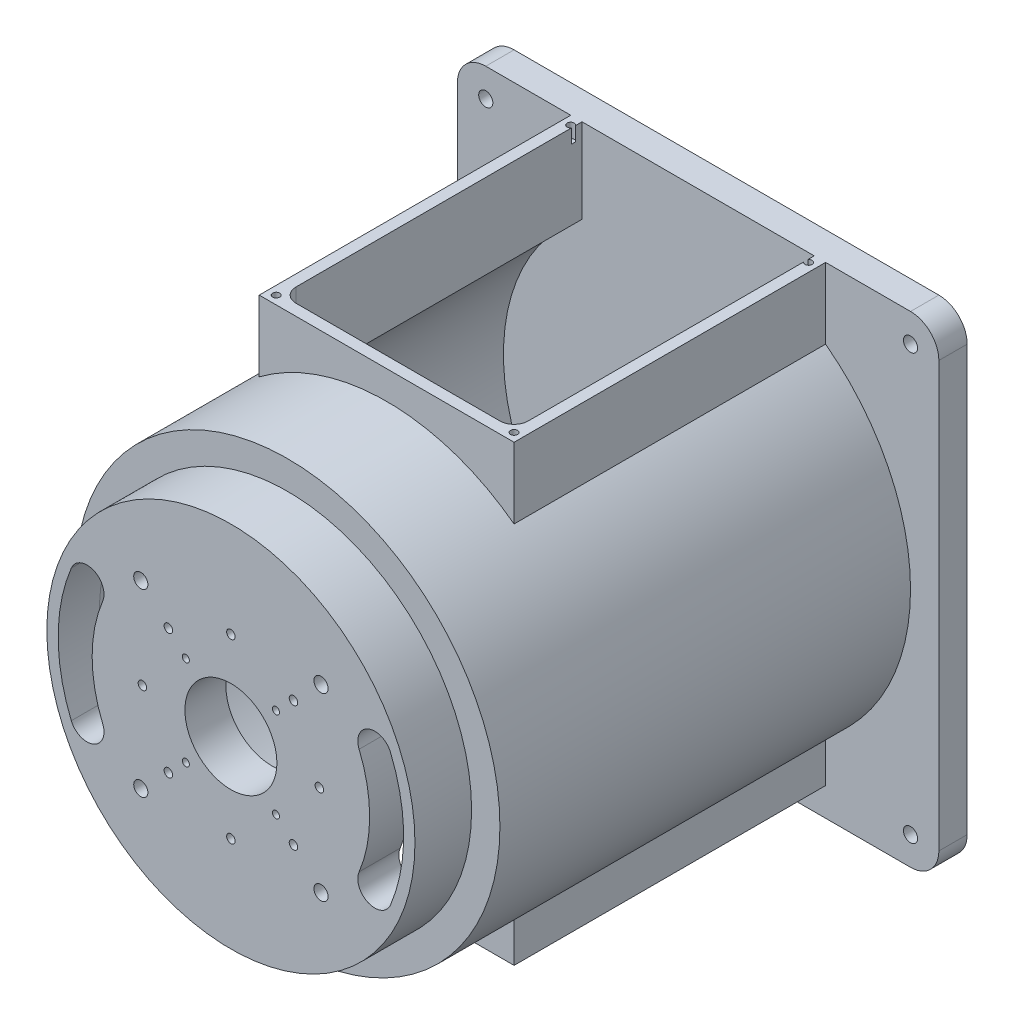
SolidWorks part; units mm, degrees
material "Cast Stainless Steel"
ref_plane "Front Plane" through (0, 0, 0) normal (0, 0, 1) x (1, 0, 0)
ref_plane "Top Plane" through (0, 0, 0) normal (0, 1, 0) x (1, 0, 0)
ref_plane "Right Plane" through (0, 0, 0) normal (1, 0, 0) x (0, 0, -1)
other "Center of Mass"
sketch "Sketch1" plane through (0, 0, 0) normal (0, 1, 0) x (1, 0, 0)
  line L1 (150, -170) -> (-150, -170)
  line L2 (170, -150) -> (170, 150)
  line L3 (150, 170) -> (-150, 170)
  line L4 (-170, -150) -> (-170, 150)
  line L5 (170, -170) -> (-170, 170) construction
  line L6 (170, 170) -> (-170, -170) construction
  arc A0 (170, -150) -> (150, -170) centre (150, -150) cw
  arc A1 (-170, -150) -> (-150, -170) centre (-150, -150) ccw
  arc A2 (150, 170) -> (170, 150) centre (150, 150) cw
  arc A3 (-150, 170) -> (-170, 150) centre (-150, 150) ccw
  point P0 (0, 0)
  dimension "D3" = 20
  dimension "D1" = 340
  dimension "D2" = 340
extrude "Boss-Extrude1" add sketch "Sketch1" along normal blind 20
sketch "Sketch2" plane through (0, 20, 0) normal (0, 1, 0) x (1, 0, 0)
  line L4 (170, -150) -> (170, 150)
  line L5 (150, 170) -> (-150, 170)
  line L6 (-170, 150) -> (-170, -150)
  line L7 (-150, -170) -> (150, -170)
  line L8 (170, -150) -> (170, 150)
  line L9 (150, 170) -> (-150, 170)
  line L10 (-170, 150) -> (-170, -150)
  line L11 (-150, -170) -> (150, -170)
  line L12 (-150, 0) -> (-150, -90)
  line L13 (-150, -90) -> (-120, -90)
  line L14 (120, -90) -> (150, -90)
  line L15 (0, 0) -> (-150, 0) construction
  line L16 (150, -150) -> (150, 150)
  line L17 (150, 150) -> (-150, 150)
  line L18 (-150, 150) -> (-150, -150)
  line L19 (-150, -150) -> (150, -150)
  line L20 (150, -150) -> (150, 150)
  line L21 (150, 150) -> (-150, 150)
  line L22 (-150, 150) -> (-150, -150)
  line L23 (-150, -150) -> (150, -150)
  line L24 (150, -90) -> (170, -90)
  line L25 (150, 90) -> (170, 90)
  line L26 (120, 90) -> (150, 90)
  line L27 (-150, 90) -> (-120, 90)
  arc A4 (150, -170) -> (170, -150) centre (150, -150) ccw
  arc A5 (170, 150) -> (150, 170) centre (150, 150) ccw
  arc A6 (-150, 170) -> (-170, 150) centre (-150, 150) ccw
  arc A7 (-170, -150) -> (-150, -170) centre (-150, -150) ccw
  arc A8 (150, -170) -> (170, -150) centre (150, -150) ccw
  arc A9 (170, 150) -> (150, 170) centre (150, 150) ccw
  arc A10 (-150, 170) -> (-170, 150) centre (-150, 150) ccw
  arc A11 (-170, -150) -> (-150, -170) centre (-150, -150) ccw
  circle A12 centre (0, 0) radius 150
  dimension "D3" = 30
  dimension "D1" = 0
  dimension "D2" = 20
extrude "Boss-Extrude2" add sketch "Sketch2" along normal blind 220 contours A12 | A12 L12 L13 | A12 L14 L20 | L25 L20 L24 L8 | A12 L20 L26 | A12 L27 L22 region at (160, 20, 0) region at (141.1785, 20, 67.9748) region at (141.1785, 20, -67.9748) region at (0, 20, 0) region at (-141.1785, 20, 67.9748) region at (-141.1785, 20, -67.9748)
sketch "Sketch3" plane through (0, 240, 0) normal (0, 1, 0) x (1, 0, 0)
  line L6 (170, -90) -> (170, 90)
  line L7 (170, 90) -> (120, 90)
  line L8 (-120, 90) -> (-150, 90)
  line L9 (-150, 90) -> (-150, -90)
  line L10 (-150, -90) -> (-120, -90)
  line L11 (120, -90) -> (170, -90)
  line L12 (170, -90) -> (170, 90)
  line L13 (170, 90) -> (120, 90)
  line L14 (-120, 90) -> (-150, 90)
  line L15 (-150, 90) -> (-150, -90)
  line L16 (-150, -90) -> (-120, -90)
  line L17 (120, -90) -> (170, -90)
  circle A0 centre (0, 0) radius 150
  arc A2 (120, 90) -> (-120, 90) centre (0, 0) ccw
  arc A3 (-120, -90) -> (120, -90) centre (0, 0) ccw
  arc A4 (120, 90) -> (-120, 90) centre (0, 0) ccw
  arc A5 (-120, -90) -> (120, -90) centre (0, 0) ccw
  arc M11 (120, 90) -> (-120, 90) centre (0, 0) ccw
  arc M15 (-120, -90) -> (120, -90) centre (0, 0) ccw
  dimension "D1" = 0
extrude "Boss-Extrude3" add sketch "Sketch3" along normal blind 70 contours A0 M15 M11 region at (0, 240, 0)
sketch "Sketch4" plane through (0, 310, 0) normal (0, 1, 0) x (1, 0, 0)
  circle A1 centre (0, 0) radius 150
  circle A2 centre (0, 0) radius 150
  circle A4 centre (0, 0) radius 130
  circle A5 centre (0, 0) radius 130
  dimension "D1" = 0
  dimension "D2" = 20
extrude "Boss-Extrude4" add sketch "Sketch4" along normal blind 40 contours A5 region at (0, 310, 0)
sketch "Sketch18" plane through (0, 20, 0) normal (0, 1, 0) x (1, 0, 0)
  circle A0 centre (0, 0) radius 137.5
  dimension "D1" = 275
extrude "Cut-Extrude6" cut sketch "Sketch18" along normal blind 256
ref_point "Point1"
move or copy body "Body-Move/Copy1" bodies to move or copy 115 copy no rotation origin (0, 0, 0) rotation axis (1, 0, 0) rotation angle 90
move or copy body "Body-Move/Copy2" bodies to move or copy 118 copy no rotation origin (0, 0, 0) rotation axis (0, 0, -1) rotation angle 90
move or copy body "Body-Move/Copy3" bodies to move or copy 119 copy no rotation origin (0, 0, 0) rotation axis (0, 0, 1) rotation angle 180
sketch "Sketch19" plane through (0, 0, 350) normal (0, 0, 1) x (1, 0, 0)
  circle A0 centre (0, 0) radius 32.5
  dimension "D1" = 65
extrude "Cut-Extrude7" cut sketch "Sketch19" against normal up to surface (74 mm away) up to face at (137.5, 0, 276)
sketch "Sketch20" plane through (0, 0, 0) normal (0, 0, -1) x (-1, 0, 0)
  line L1 (-150, 150) -> (150, 150)
  line L2 (-150, 150) -> (-150, -150)
  line L3 (-150, -150) -> (150, -150)
  line L4 (150, 150) -> (150, -150)
  line L5 (-150, 150) -> (150, -150) construction
  line L6 (-150, -150) -> (150, 150) construction
  circle A0 centre (150, -150) radius 5
  circle A1 centre (-150, -150) radius 5
  circle A2 centre (-150, 150) radius 5
  circle A3 centre (150, 150) radius 5
  point P0 (0, 0)
  point P7 (150, -150)
  point P8 (-150, -150)
  point P9 (150, 150)
  point P10 (-150, 150)
  dimension "D3" = 10
  dimension "D4" = 10
  dimension "D5" = 10
  dimension "D6" = 10
  dimension "D1" = 300
  dimension "D2" = 300
extrude "Cut-Extrude8" cut sketch "Sketch20" against normal up to surface (20 mm away) contours L3 A0 L4 | L4 A0 L3 | L2 A1 L3 | L3 A1 L2 | L1 A2 L2 | L2 A2 L1 | L4 A3 L1 | L1 A3 L4 region at (150.7074, 150.7074, 0) region at (147.8779, 147.8779, 0) region at (-150.7074, 150.7074, 0) region at (-147.8779, 147.8779, 0) region at (147.8779, -147.8779, 0) region at (150.7074, -150.7074, 0) region at (-150.7074, -150.7074, 0) region at (-147.8779, -147.8779, 0) up to face at (0, 2.5, 20)
sketch "Sketch26" plane through (0, 0, 350) normal (0, 0, 1) x (1, 0, 0)
  line L0 (0, 0) -> (0, 110) construction
  line L1 (0, 0) -> (42.0952, 101.6267) construction
  line L2 (0, 0) -> (101.6267, -42.0952) construction
  line L3 (0, 0) -> (110, 0) construction
  line L4 (0, 0) -> (101.6267, 42.0952) construction
  circle A0 centre (0, 0) radius 110
  circle A1 centre (0, 0) radius 130
  circle A2 centre (0, 0) radius 130
  circle A3 centre (101.6267, -42.0952) radius 12
  circle A4 centre (110, 0) radius 12
  circle A5 centre (0, 0) radius 98
  circle A6 centre (0, 0) radius 122
  circle A7 centre (101.6267, 42.0952) radius 12
  dimension "D2" = 220
  dimension "D4" = 24
  dimension "D5" = 24
  dimension "D8" = 196
  dimension "D9" = 244
  dimension "D10" = 24
  dimension "D3" = 22.5
  dimension "D6" = 22.5
  dimension "D7" = 22.5
  dimension "D1" = 0
extrude "Cut-Extrude11" cut sketch "Sketch26" against normal up to surface (74 mm away) contours A0 A3 | A0 A3 | A3 A6 A4 A0 | A5 A3 A0 A4 | A0 A4 | A7 A5 A4 A0 | A7 A0 A4 A6 | A7 A0 | A0 A7 | A0 A4 region at (104.791, 0, 350) region at (114.9732, 0, 350) region at (101.2141, 20.1327, 350) region at (114.2829, 22.7323, 350) region at (114.2829, -22.7323, 350) region at (101.2141, -20.1327, 350) region at (96.8142, 40.1018, 350) region at (106.2214, 43.9984, 350) region at (106.2214, -43.9984, 350) region at (96.8142, -40.1018, 350) up to face at (32.5, 0, 276)
sketch "Sketch29" plane through (0, 0, 276) normal (0, 0, -1) x (-1, 0, 0)
  circle A0 centre (0, 0) radius 122.5
  circle A1 centre (0, 0) radius 137.5
  circle A2 centre (0, 0) radius 137.5
  arc M2 (-90.5402, -37.503) -> (-112.7133, -46.6874) centre (-101.6267, -42.0952) cw
  arc M3 (-112.7133, -46.6874) -> (-112.7133, 46.6874) centre (0, 0) cw
  arc M4 (-112.7133, 46.6874) -> (-90.5402, 37.503) centre (-101.6267, 42.0952) cw
  arc M5 (-90.5402, 37.503) -> (-90.5402, -37.503) centre (0, 0) ccw
  circle M6 centre (0, 0) radius 32.5
  dimension "D1" = 0
  dimension "D2" = 15
extrude "Cut-Extrude12" cut sketch "Sketch29" against normal blind 45 contours A0 M5 M2 M3 M4 M6 region at (122.1535, 0, 276)
mirror "Mirror1" about plane through (0, 0, 0) normal (1, 0, 0) of "Cut-Extrude11"
sketch "Sketch33" plane through (0, -150, 0) normal (0, -1, 0) x (1, 0, 0)
  line L5 (-90, 20) -> (90, 20)
  line L6 (90, 20) -> (90, 240)
  line L7 (90, 240) -> (0, 240)
  line L8 (0, 240) -> (-90, 240)
  line L9 (-90, 240) -> (-90, 20)
  line L10 (-90, 20) -> (90, 20)
  line L11 (90, 20) -> (90, 240)
  line L12 (90, 240) -> (0, 240)
  line L13 (0, 240) -> (-90, 240)
  line L14 (-90, 240) -> (-90, 20)
  line L15 (-82, 28) -> (-82, 20)
  line L16 (82, 28) -> (82, 20)
  line L20 (-82, 28) -> (82, 28)
  line L21 (82, 28) -> (82, 232)
  line L22 (82, 232) -> (0, 232)
  line L23 (0, 232) -> (-82, 232)
  line L24 (-82, 232) -> (-82, 28)
  line L26 (82, 28) -> (82, 222)
  line L27 (72, 232) -> (0, 232)
  line L28 (0, 232) -> (-72, 232)
  line L29 (-82, 222) -> (-82, 28)
  arc A0 (82, 222) -> (72, 232) centre (72, 222) ccw
  arc A1 (-82, 222) -> (-72, 232) centre (-72, 222) cw
  dimension "D3" = 10
  dimension "D1" = 0
  dimension "D2" = 8
extrude "Cut-Extrude13" cut sketch "Sketch33" against normal up to surface (320 mm away) contours A1 L29 L15 L10 L16 L26 A0 L27 L28 region at (0, -150, 24) region at (0, -150, 129.8718) up to face at (170, 0, 10)
sketch "Sketch35" plane through (0, 170, 0) normal (0, 1, 0) x (1, 0, 0)
  line L0 (0, -240) -> (0, -232) construction
  line L1 (-90, -240) -> (-84, -240)
  line L2 (-90, -240) -> (-90, -234)
  line L3 (-90, -234) -> (-84, -234)
  line L4 (-84, -240) -> (-84, -234)
  line L5 (-90, -20) -> (-84, -20)
  line L6 (-90, -20) -> (-90, -32)
  line L7 (-90, -32) -> (-84, -32)
  line L8 (150, 0) -> (-150, 0)
  line L9 (-150, 0) -> (-150, -20)
  line L10 (-150, -20) -> (-90, -20)
  line L11 (-90, -20) -> (-90, -240)
  line L12 (-90, -240) -> (90, -240)
  line L13 (90, -240) -> (90, -20)
  line L14 (90, -20) -> (150, -20)
  line L15 (150, -20) -> (150, 0)
  line L16 (150, 0) -> (-150, 0)
  line L17 (-150, 0) -> (-150, -20)
  line L18 (-150, -20) -> (-90, -20)
  line L19 (-90, -20) -> (-90, -240)
  line L20 (-90, -240) -> (90, -240)
  line L21 (90, -240) -> (90, -20)
  line L22 (90, -20) -> (150, -20)
  line L23 (150, -20) -> (150, 0)
  line L24 (-84, -20) -> (-84, -32)
  line L25 (-72, -232) -> (72, -232) construction
  circle A0 centre (-84, -234) radius 2.5
  circle A1 centre (-84, -26) radius 2.5
  circle A2 centre (84, -26) radius 2.5
  circle A3 centre (84, -234) radius 2.5
  point P25 (-86, -23.9982)
  line M24 (82, -20) -> (82, -222)
  dimension "D4" = 5
  dimension "D7" = 5
  dimension "D2" = 6
  dimension "D3" = 6
  dimension "D5" = 6
  dimension "D6" = 6
  dimension "D1" = 0
extrude "Cut-Extrude14" cut sketch "Sketch35" against normal blind 10 contours L4 A0 L3 | L3 A0 L4 | L24 A1 L5 | A3 | A2 | L24 A1 | A2 M24 region at (-85.061, 170, 235.061) region at (-83.6463, 170, 233.6463) region at (-85.061, 170, 26) region at (-82.939, 170, 26) region at (84.1209, 170, 26) region at (81.7982, 170, 26) region at (84, 170, 234)
sketch "Sketch36" plane through (0, -150, 0) normal (0, -1, 0) x (1, 0, 0)
  line L0 (0, 232) -> (0, 240) construction
  line L1 (-90, 240) -> (-84, 240)
  line L2 (-90, 240) -> (-90, 234)
  line L3 (-90, 234) -> (-84, 234)
  line L4 (-84, 240) -> (-84, 234)
  line L5 (-90, 20) -> (-84, 20)
  line L6 (-90, 20) -> (-90, 26)
  line L7 (-90, 26) -> (-84, 26)
  line L8 (-84, 20) -> (-84, 26)
  line L9 (82, 222) -> (82, 20)
  line L10 (82, 20) -> (90, 20)
  line L11 (90, 20) -> (90, 240)
  line L12 (90, 240) -> (0, 240)
  line L13 (0, 240) -> (-90, 240)
  line L14 (-90, 240) -> (-90, 20)
  line L15 (-90, 20) -> (-82, 20)
  line L16 (-82, 20) -> (-82, 222)
  line L17 (-72, 232) -> (72, 232)
  line L18 (82, 222) -> (82, 20)
  line L19 (82, 20) -> (90, 20)
  line L20 (90, 20) -> (90, 240)
  line L21 (90, 240) -> (0, 240)
  line L22 (0, 240) -> (-90, 240)
  line L23 (-90, 240) -> (-90, 20)
  line L24 (-90, 20) -> (-82, 20)
  line L25 (-82, 20) -> (-82, 222)
  line L26 (-72, 232) -> (72, 232)
  circle A0 centre (-84, 234) radius 2.5
  circle A1 centre (-84, 26) radius 2.5
  arc A2 (-72, 232) -> (-82, 222) centre (-72, 222) ccw
  arc A3 (82, 222) -> (72, 232) centre (72, 222) ccw
  arc A4 (-72, 232) -> (-82, 222) centre (-72, 222) ccw
  arc A5 (82, 222) -> (72, 232) centre (72, 222) ccw
  circle A6 centre (84, 26) radius 2.5
  circle A7 centre (84, 234) radius 2.5
  dimension "D4" = 5
  dimension "D7" = 5
  dimension "D2" = 6
  dimension "D3" = 6
  dimension "D5" = 6
  dimension "D6" = 6
  dimension "D1" = 0
extrude "Cut-Extrude15" cut sketch "Sketch36" against normal blind 10 contours L3 A0 L4 | L4 A0 L3 | A7 | A6 L18 | A6 L18 | L25 A1 L7 L8 | L7 A1 L8 | L25 A1 region at (-83.6463, -150, 233.6463) region at (-85.061, -150, 235.061) region at (-83.7841, -150, 26.3801) region at (-85.061, -150, 24.939) region at (-81.7982, -150, 26) region at (81.7982, -150, 26) region at (84.1209, -150, 26) region at (84, -150, 234)
sketch "Sketch37" plane through (0, 0, 350) normal (0, 0, 1) x (1, 0, 0)
  line L0 (0, 0) -> (90, 0)
  line L1 (90, 0) -> (0, -90)
  line L2 (0, -90) -> (0, 0)
  line L3 (0, 0) -> (63.6396, -63.6396)
  circle A0 centre (0, 0) radius 45
  circle A1 centre (0, 0) radius 130
  circle A2 centre (0, 0) radius 130
  circle A3 centre (0, 0) radius 62.5
  circle A4 centre (0, 0) radius 90
  circle A5 centre (63.6396, -63.6396) radius 5
  circle A6 centre (44.1942, -44.1942) radius 3
  circle A7 centre (31.8198, -31.8198) radius 2.5
  circle A8 centre (-63.6396, -63.6396) radius 5
  circle A9 centre (-63.6396, 63.6396) radius 5
  circle A10 centre (63.6396, 63.6396) radius 5
  circle A14 centre (0, -62.5) radius 3
  circle A15 centre (-44.1942, -44.1942) radius 3
  circle A16 centre (-62.5, 0) radius 3
  circle A17 centre (-44.1942, 44.1942) radius 3
  circle A18 centre (0, 62.5) radius 3
  circle A19 centre (44.1942, 44.1942) radius 3
  circle A20 centre (62.5, 0) radius 3
  circle A21 centre (-31.8198, -31.8198) radius 2.5
  circle A22 centre (-31.8198, 31.8198) radius 2.5
  circle A23 centre (31.8198, 31.8198) radius 2.5
  dimension "D2" = 180
  dimension "D3" = 125
  dimension "D4" = 90
  dimension "D5" = 10
  dimension "D6" = 6
  dimension "D7" = 5
  dimension "D1" = 0
  dimension "D8" = 4
  dimension "D9" = 8
  dimension "D10" = 4
extrude "Cut-Extrude16" cut sketch "Sketch37" against normal up to surface (29 mm away) contours A4 A10 | A4 A10 | A3 A19 | A3 A19 | A0 A23 | A0 A23 | A3 A20 L0 | L0 A20 A3 | A3 A20 L0 | L0 A20 A3 | L3 A5 A4 | A4 A5 | A4 A5 L3 | L3 A6 A3 | L1 A6 L3 | A3 A6 L1 L3 | L3 A6 L1 | L1 A6 A3 L3 | A3 A6 L3 | L3 A7 A0 | A0 A7 L3 | L3 A7 A0 | A0 A7 L3 | A3 A14 L2 | L2 A14 A3 | A3 A14 L2 | L2 A14 A3 | A4 A8 | A4 A8 | A3 A15 | A3 A15 | A0 A21 | A0 A21 | A0 A22 | A0 A22 | A3 A17 | A3 A17 | A4 A9 | A4 A9 | A3 A16 | A3 A16 | A3 A18 | A3 A18 | A23 region at (31.8042, -30.3174, 350) region at (30.3174, -31.8042, 350) region at (61.2139, 1.2632, 350) region at (61.2139, -1.2632, 350) region at (31.0608, 31.0608, 350) region at (32.5612, 32.5612, 350) region at (33.3181, -31.8042, 350) region at (1.2632, -61.2139, 350) region at (-1.2632, -61.2139, 350) region at (-32.5612, -32.5612, 350) region at (-31.0608, -31.0608, 350) region at (31.8042, -33.3181, 350) region at (63.7602, 1.2831, 350) region at (63.7602, -1.2831, 350) region at (1.2831, -63.7602, 350) region at (-1.2831, -63.7602, 350) region at (43.2847, 43.2847, 350) region at (45.0853, 45.0853, 350) region at (45.6301, -43.5364, 350) region at (44.178, -42.3915, 350) region at (-31.0608, 31.0608, 350) region at (-32.5612, 32.5612, 350) region at (42.3915, -44.178, 350) region at (43.5364, -45.6301, 350) region at (-45.0853, -45.0853, 350) region at (-43.2847, -43.2847, 350) region at (46.3232, -44.7634, 350) region at (44.7634, -46.3232, 350) region at (62.1215, 62.1215, 350) region at (65.1223, 65.1223, 350) region at (65.1223, -65.1223, 350) region at (63.6083, -60.6347, 350) region at (0, 61.2139, 350) region at (0, 63.7602, 350) region at (-65.1223, -65.1223, 350) region at (-62.1215, -62.1215, 350) region at (60.6347, -63.6083, 350) region at (-63.7602, 0, 350) region at (-61.2139, 0, 350) region at (-62.1215, 62.1215, 350) region at (-65.1223, 65.1223, 350) region at (-43.2847, 43.2847, 350) region at (-45.0853, 45.0853, 350) up to face at (-103.5173, 0, 321)
